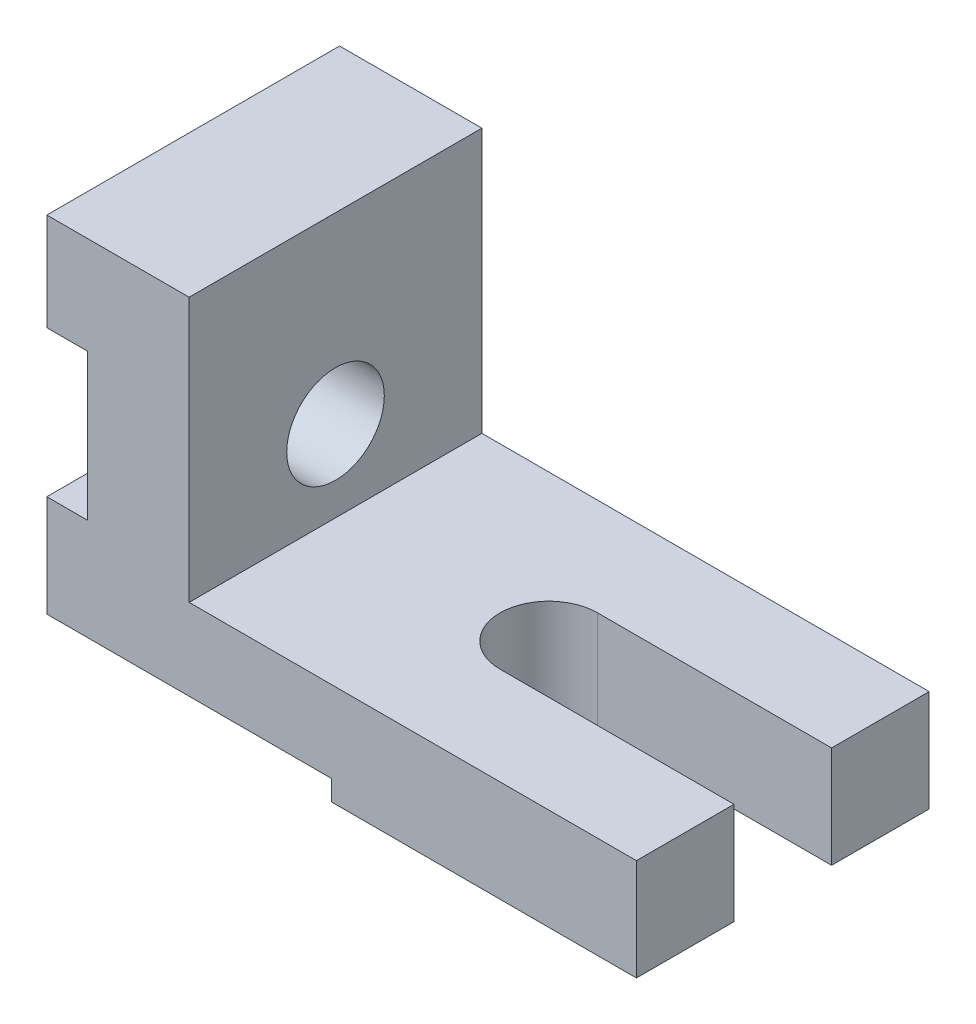
SolidWorks part; units mm, degrees
ref_plane "Front Plane" through (0, 0, 0) normal (0, 0, 1) x (1, 0, 0)
ref_plane "Top Plane" through (0, 0, 0) normal (0, 1, 0) x (1, 0, 0)
ref_plane "Right Plane" through (0, 0, 0) normal (1, 0, 0) x (0, 0, -1)
sketch "Sketch2" plane through (0, 0, 0) normal (0, 1, 0) x (1, 0, 0)
  line L0 (145, 48) -> (87.4544, 48)
  line L1 (0, 0) -> (145, 0)
  line L2 (0, 0) -> (0, 72)
  line L3 (0, 72) -> (145, 72)
  line L4 (145, 0) -> (145, 72)
  line L5 (145, 24) -> (87.4544, 24)
  line L6 (35, 72) -> (35, 0)
  arc A0 (87.4544, 48) -> (87.4544, 24) centre (87.4544, 36) ccw
  dimension "D5" = 35
  dimension "D1" = 145
  dimension "D2" = 72
  dimension "D3" = 24
  dimension "D4" = 24
extrude "Boss-Extrude1" add sketch "Sketch2" along normal blind 25 contours A0 L0 L4 L3 L6 L1 L5 region at (116.2272, 0, -49.3147)
extrude "Boss-Extrude2" add sketch "Sketch2<3>" along normal blind 90 contours L6 L3 L2 L1 region at (17.5, 0, -36)
sketch "Sketch2<3>" plane through (0, 0, 0) normal (0, 1, 0) x (1, 0, 0) same geometry as "Sketch2"
sketch "Sketch4" plane through (0, 0, 0) normal (0, 0, 1) x (1, 0, 0)
  line L0 (0, 5) -> (70, 5)
  line L1 (0, 90) -> (0, 0) construction
  line L2 (70, 5) -> (70, 0)
  line L3 (0, 0) -> (145, 0) construction
  line L4 (0, 5) -> (0, 0)
  line L5 (0, 0) -> (70, 0)
  dimension "D1" = 70
  dimension "D2" = 5
extrude "Cut-Extrude1" cut sketch "Sketch4" against normal blind 50
sketch "Sketch5" plane through (0, 0, 0) normal (-1, 0, 0) x (0, 0, 1)
  line L0 (-36, 94.4371) -> (-36, -2.1167) construction
  line L1 (-72, 90) -> (-72, 0) construction
  line L2 (-72, 66) -> (-72, 30)
  line L3 (-101.3575, 45) -> (46.5026, 45) construction
  line L4 (0, 90) -> (-72, 90) construction
  line L5 (-72, 30) -> (-61.9808, 30)
  line L6 (-50, 0) -> (-72, 0) construction
  line L7 (0, 30) -> (-10.0192, 30)
  line L8 (-72, 66) -> (-57.4243, 66)
  line L9 (-14.5757, 66) -> (0, 66)
  line L10 (0, 90) -> (0, 5) construction
  line L11 (0, 66) -> (0, 30)
  circle A0 centre (-36, 45) radius 12
  arc A1 (-61.9808, 30) -> (-10.0192, 30) centre (-36, 45) ccw
  arc A2 (-14.5757, 66) -> (-57.4243, 66) centre (-36, 45) ccw
  dimension "D2" = 60
  dimension "D3" = 24
  dimension "D1" = 36
  dimension "D4" = 45
  dimension "D5" = 45
  dimension "D6" = 30
  dimension "D7" = 24
  dimension "D8" = 24
extrude "Cut-Extrude2" cut sketch "Sketch5" against normal blind 10
sketch "Sketch6" plane through (0, 0, 0) normal (-1, 0, 0) x (0, 0, 1)
  circle A0 centre (-36, 45) radius 12
extrude "Cut-Extrude3" cut sketch "Sketch6" against normal up to next
